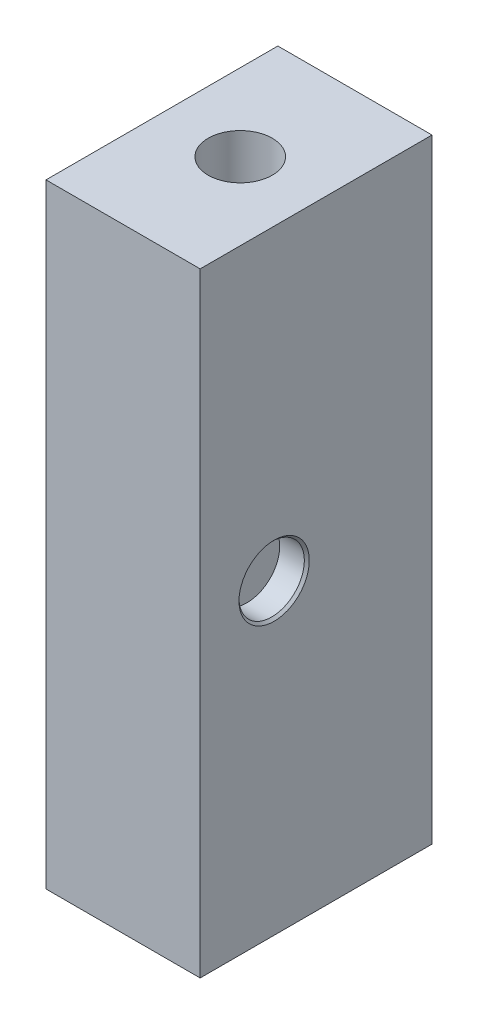
SolidWorks part; units mm, degrees
material "ABS"
ref_plane "Front Plane" through (0, 0, 0) normal (0, 0, 1) x (1, 0, 0)
ref_plane "Top Plane" through (0, 0, 0) normal (0, 1, 0) x (1, 0, 0)
ref_plane "Right Plane" through (0, 0, 0) normal (1, 0, 0) x (0, 0, -1)
sketch "Sketch1" plane through (0, 0, 0) normal (0, 1, 0) x (1, 0, 0)
  line L0 (-3.75, -9.5) -> (50.75, -9.5) construction
  line L1 (6.25, -9.5) -> (-6.25, -9.5)
  line L2 (6.25, -9.5) -> (6.25, 9.3)
  line L3 (6.25, 9.5) -> (-6.25, 9.5) construction
  line L4 (-6.25, -9.5) -> (-6.25, 9.3)
  line L5 (6.25, -9.5) -> (-6.25, 9.5) construction
  line L6 (6.1184, 9.3) -> (-6.25, -9.5) construction
  line L7 (114.75, 9.5) -> (-6.25, 9.5) construction
  line L8 (-6.25, 9.3) -> (6.25, 9.3)
  line L9 (-6.25, 9.3) -> (-6.25, 9.5) construction
  line L10 (6.25, 9.3) -> (6.25, 9.5) construction
  line L11 (6.25, 9.5) -> (6.1184, 9.3) construction
  circle A0 centre (0, 0) radius 2.6
  circle A1 centre (0, 0) radius 2.6 construction
  point P0 (0, 0)
  dimension "D4" = 5.2
  dimension "D1" = 12.5
  dimension "D2" = 0.2
extrude "Boss-Extrude1" add sketch "Sketch1" along normal mid plane 49.8
sketch "Sketch2" plane through (6.25, 0, 0) normal (1, 0, 0) x (0, 0, -1)
  line L0 (-9.5, -24.9) -> (-9.5, 24.9) construction
  line L3 (9.5, -25) -> (9.5, 25) construction
  circle A0 centre (-3.5, 0) radius 2.65
  dimension "D1" = 5.3
  dimension "D2" = 13
  dimension "D3" = 3.35
extrude "Cut-Extrude1" cut sketch "Sketch2" against normal blind 2.2
chamfer "Chamfer1" distance 0.2 angle 45 1 edges at (6.25, 0, 0.85)
